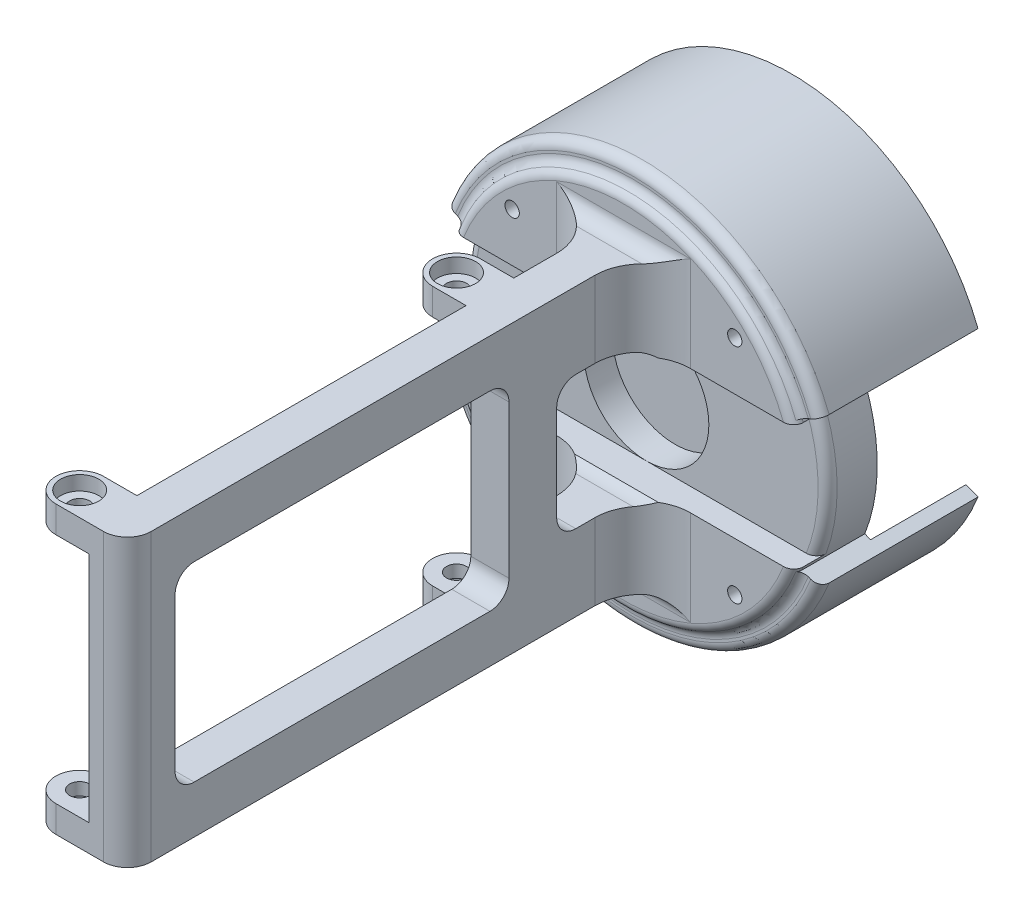
SolidWorks part; units mm, degrees
material "Esun Hard Tough Resin"
ref_plane "Front Plane" through (0, 0, 0) normal (0, 0, 1) x (1, 0, 0)
ref_plane "Top Plane" through (0, 0, 0) normal (0, 1, 0) x (1, 0, 0)
ref_plane "Right Plane" through (0, 0, 0) normal (1, 0, 0) x (0, 0, -1)
sketch "Sketch1" plane through (0, 0, 0) normal (0, 0, 1) x (1, 0, 0)
  line L0 (-11.6673, 11.6673) -> (11.6673, -11.6673) construction
  line L1 (11.6673, 11.6673) -> (-11.6673, -11.6673) construction
  line L2 (0, 16.5) -> (0, -16.5) construction
  circle A0 centre (0, 0) radius 19
  circle A1 centre (0, 0) radius 9 construction
  circle A2 centre (0, 0) radius 16.5 construction
  circle A3 centre (-11.6673, 11.6673) radius 1
  circle A4 centre (11.6673, 11.6673) radius 1
  circle A5 centre (11.6673, -11.6673) radius 1
  circle A6 centre (-11.6673, -11.6673) radius 1
  point P17 (0, 0)
  point P18 (0, 0)
  dimension "D1" = 38
  dimension "D2" = 18
  dimension "D3" = 33
  dimension "D4" = 2
  dimension "D5" = 90
  dimension "D6" = 45
extrude "Boss-Extrude1" add sketch "Sketch1" along normal blind 1.6
sketch "Sketch2" plane through (0, 0, 1.6) normal (0, 0, 1) x (1, 0, 0)
  circle A0 centre (0, 0) radius 19
  circle A1 centre (11.6673, -11.6673) radius 1 construction
  circle A2 centre (11.6673, 11.6673) radius 1 construction
  circle A3 centre (-11.6673, 11.6673) radius 1 construction
  circle A4 centre (-11.6673, -11.6673) radius 1 construction
  circle A5 centre (11.6673, -11.6673) radius 1 construction
  circle A6 centre (11.6673, 11.6673) radius 1 construction
  circle A7 centre (-11.6673, 11.6673) radius 1 construction
  circle A8 centre (-11.6673, -11.6673) radius 1 construction
  circle A9 centre (-11.6673, -11.6673) radius 0.75
  circle A10 centre (-11.6673, 11.6673) radius 0.75
  circle A11 centre (11.6673, 11.6673) radius 0.75
  circle A12 centre (11.6673, -11.6673) radius 0.75
  circle A13 centre (0, 0) radius 19 construction
  dimension "D1" = 1.5
extrude "Boss-Extrude2" add sketch "Sketch2" along normal blind 6
sketch "Sketch8" plane through (0, 0, 0) normal (0, 0, -1) x (-1, 0, 0)
  circle A0 centre (0, 0) radius 12.75
  dimension "D1" = 25.5
extrude "Cut-Extrude4" cut sketch "Sketch8" against normal blind 1
sketch "Sketch3" plane through (0, 0, 7.6) normal (0, 0, 1) x (1, 0, 0)
  circle A0 centre (0, 0) radius 6.55
  dimension "D1" = 13.1
extrude "Cut-Extrude1" cut sketch "Sketch3" against normal offset from surface (5.4 mm away) 1.2 up to face at (-12.75, 0, 1)
sketch "Sketch4" plane through (0, 0, 0) normal (1, 0, 0) x (0, 0, -1)
  line L0 (-7.6, 15) -> (-61.6, 15)
  line L1 (-7.6, 19) -> (-7.6, -19) construction
  line L2 (-61.6, 15) -> (-61.6, -15)
  line L3 (-61.6, -15) -> (-7.6, -15)
  line L4 (-7.6, -15) -> (-7.6, -7)
  line L5 (-7.6, -7) -> (-16.6, -7)
  line L6 (-16.6, -7) -> (-16.6, 7)
  line L7 (-16.6, 7) -> (-7.6, 7)
  line L8 (-7.6, 7) -> (-7.6, 15)
  point P6 (-16.6, 0)
  point P11 (-61.6, 0)
  dimension "D1" = 14
  dimension "D2" = 9
  dimension "D3" = 30
  dimension "D4" = 45
extrude "Boss-Extrude3" add sketch "Sketch4" along normal mid plane 4
fillet "Fillet1" radius 5 4 edges at (-2, -11, 7.6) (2, -11, 7.6) (2, 11, 7.6) (-2, 11, 7.6)
fillet "Fillet2" radius 2 2 edges at (0, -7, 16.6) (0, 7, 16.6)
ref_plane "Plane1" through (2, 15, 12.6) normal (0, 0, 1) x (1, 0, 0)
sketch "Sketch5" plane through (-2, 14.5, 12.6) normal (1, 0, 0) x (0, 0, -1)
  line L0 (0, 0.5) -> (-49, 0.5) construction
  line L1 (-49, 0.5) -> (-44, 0.5)
  line L2 (-49, 0.5) -> (-49, -2.3)
  line L3 (-49, -2.3) -> (-44, -2.3)
  line L4 (-44, 0.5) -> (-44, -2.3)
  line L5 (-9.5, 0.5) -> (-4.5, 0.5)
  line L6 (-9.5, 0.5) -> (-9.5, -2.3)
  line L7 (-9.5, -2.3) -> (-4.5, -2.3)
  line L8 (-4.5, 0.5) -> (-4.5, -2.3)
  line L9 (-1000, -14.5) -> (49000, -14.5) construction
  line L11 (-9.5, -26.7) -> (-4.5, -26.7)
  line L12 (-4.5, -29.5) -> (-4.5, -26.7)
  line L13 (-9.5, -29.5) -> (-4.5, -29.5)
  line L14 (-9.5, -29.5) -> (-9.5, -26.7)
  line L15 (-49, -26.7) -> (-44, -26.7)
  line L16 (-44, -29.5) -> (-44, -26.7)
  line L17 (-49, -29.5) -> (-44, -29.5)
  line L18 (-49, -29.5) -> (-49, -26.7)
  point P12 (-46.5, -2.3)
  point P17 (-7, -2.3)
  dimension "D1" = 39.5
  dimension "D2" = 5
  dimension "D3" = 2.8
extrude "Boss-Extrude4" add sketch "Sketch5" against normal blind 6
sketch "Sketch6" plane through (0, 15, 0) normal (0, 1, 0) x (1, 0, 0)
  line L0 (-8, -56.6) -> (-8, -61.6) construction
  line L1 (-8, -56.6) -> (-8, -61.6) construction
  line L2 (-8, -17.1) -> (-8, -22.1) construction
  line L3 (-8, -17.1) -> (-8, -22.1) construction
  circle A0 centre (-5.5, -59.1) radius 1.05
  circle A1 centre (-5.5, -19.6) radius 1.05
  point P7 (-8, -59.1)
  point P12 (-8, -19.6)
  dimension "D1" = 2.1
  dimension "D2" = 2.5
extrude "Cut-Extrude2" cut sketch "Sketch6" against normal through all
sketch "Sketch7" plane through (0, 15, 0) normal (0, 1, 0) x (1, 0, 0)
  circle A0 centre (-5.5, -19.6) radius 2
  circle A1 centre (-5.5, -59.1) radius 2
  dimension "D1" = 4
extrude "Cut-Extrude3" cut sketch "Sketch7" against normal blind 1.5
mirror "Mirror1" about plane through (0, 0, 0) normal (0, 1, 0) of "Cut-Extrude3"
fillet "Fillet3" radius 2.5 8 edges at (-8, -13.6, 61.6) (-8, -13.6, 56.6) (-8, 13.6, 61.6) (-8, 13.6, 56.6) (-8, -13.6, 22.1) (-8, -13.6, 17.1) (-8, 13.6, 22.1) (-8, 13.6, 17.1)
fillet "Fillet4" radius 2.5 1 edges at (2, 0, 61.6)
fillet "Fillet5" radius 1.5 2 edges at (0, -15, 7.6) (0, 15, 7.6)
fillet "Fillet6" radius 2 2 edges at (0, -7, 7.6) (0, 7, 7.6)
sketch "Sketch9" plane through (0, 0, 0) normal (0, 0, -1) x (-1, 0, 0)
  line L1 (-1, 14.9737) -> (1, 14.9737)
  line L2 (-1, 14.9737) -> (-1, 18.9737)
  line L4 (1, 14.9737) -> (1, 18.9737)
  circle A0 centre (0, 0) radius 19 construction
  circle A1 centre (0, 0) radius 19
  point P7 (0, 14.9737)
  circle M7 centre (0, 0) radius 19
  dimension "D1" = 2
  dimension "D2" = 4
extrude "Boss-Extrude5" add sketch "Sketch9" along normal blind 3 contours L1 L4 L2 M7
fillet "Fillet8" radius 1 1 edges at (19, 0, 7.6)
sketch "Sketch10" plane through (-2, 0, 0) normal (-1, 0, 0) x (0, 0, 1)
  line L0 (21.6, 10) -> (21.6, -10)
  line L1 (21.6, -10) -> (56.6, -10)
  line L2 (56.6, -10) -> (56.6, 10)
  line L3 (56.6, 10) -> (21.6, 10)
  line L4 (22.1, 15) -> (56.6, 15) construction
  line L5 (56.6, -15) -> (22.1, -15) construction
  line L6 (61.6, 12.2) -> (61.6, -12.2) construction
  line L7 (16.6, -5) -> (16.6, 5) construction
  dimension "D1" = 5
  dimension "D2" = 5
  dimension "D3" = 5
  dimension "D4" = 5
extrude "Cut-Extrude5" cut sketch "Sketch10" against normal through all
fillet "Fillet9" radius 2 4 edges at (0, 10, 56.6) (0, -10, 56.6) (0, -10, 21.6) (0, 10, 21.6)
fillet "Fillet10" radius 0.4 4 edges at (1, 16.9737, -3) (0, 19, -3) (-1, 16.9737, -3) (0, 14.9737, -3)
sketch "Sketch11" plane through (0, 0, 0) normal (1, 0, 0) x (0, 0, -1)
  line L0 (-2.2, 6.55) -> (-2.2, -6.55) construction
  line L1 (-2.2, 6.55) -> (-2.2, -6.55) construction
  line L3 (-5.2, 6.55) -> (-8.3361, 6.55)
  line L4 (-5.2, 6.55) -> (-5.2, -6.55)
  line L5 (-5.2, -6.55) -> (-8.3361, -6.55)
  line L6 (-8.3361, 6.55) -> (-8.3361, -6.55)
  arc A0 (-7.6, 5) -> (-9.6, 7) centre (-9.6, 5) ccw construction
  arc A1 (-7.6, 5) -> (-9.6, 7) centre (-9.6, 5) ccw construction
  dimension "D1" = 3
extrude "Cut-Extrude6" cut sketch "Sketch11" against normal through all both and the other way through all
fillet "Fillet11" radius 1 2 edges at (-19, 0, 5.2) (19, 0, 5.2)
sketch "Sketch12" plane through (0, 0, 0) normal (0, 0, -1) x (-1, 0, 0)
  line L0 (-19.5603, 7.6417) -> (19.5603, -7.6417)
  line L1 (-19.5603, -7.6417) -> (19.5603, 7.6417)
  arc A0 (16.766, -6.55) -> (16.766, 6.55) centre (0, 0) ccw construction
  arc A1 (-16.766, 6.55) -> (-16.766, -6.55) centre (0, 0) ccw construction
  arc A2 (-1, 18.9737) -> (1, 18.9737) centre (0, 0) ccw construction
  arc A3 (16.766, -6.55) -> (16.766, 6.55) centre (0, 0) ccw construction
  arc A4 (-16.766, 6.55) -> (-16.766, -6.55) centre (0, 0) ccw construction
  arc A5 (-1, 18.9737) -> (1, 18.9737) centre (0, 0) ccw construction
  circle A6 centre (0, 0) radius 21
  circle A7 centre (0, 0) radius 19
  point P12 (0, 0)
  point P15 (0, 0)
  arc M7 (-1, 18.9737) -> (1, 18.9737) centre (0, 0) ccw
  dimension "D1" = 42
extrude "Boss-Extrude6" add sketch "Sketch12" against normal up to vertex (6.6 mm away) contours A7 L1 A6 L0 M7 | L1 A6 L0 M7
sketch "Sketch13" plane through (0, 0, 0) normal (0, 0, -1) x (-1, 0, 0)
  line L0 (-19.5603, 7.6417) -> (-18.3028, 7.1504)
  line L1 (-19.5603, -7.6417) -> (-18.3028, -7.1504)
  line L2 (-19.5603, -7.6417) -> (-17.6974, -6.9139) construction
  line L3 (19.5603, 7.6417) -> (18.3028, 7.1504)
  line L4 (19.5603, -7.6417) -> (18.3028, -7.1504)
  line L5 (17.6974, -6.9139) -> (19.5603, -7.6417) construction
  arc A0 (-19.5603, -7.6417) -> (19.5603, -7.6417) centre (0, 0) ccw construction
  arc A1 (19.5603, 7.6417) -> (-19.5603, 7.6417) centre (0, 0) ccw construction
  arc A2 (-19.5603, -7.6417) -> (19.5603, -7.6417) centre (0, 0) ccw
  arc A3 (19.5603, 7.6417) -> (-19.5603, 7.6417) centre (0, 0) ccw
  circle A4 centre (0, 0) radius 19.65
  line M3 (17.6974, 6.9139) -> (19.5603, 7.6417)
  arc M4 (19.5603, 7.6417) -> (-19.5603, 7.6417) centre (0, 0) ccw
  line M5 (-19.5603, 7.6417) -> (-17.6974, 6.9139)
  line M7 (17.6974, 6.9139) -> (19.5603, 7.6417)
  arc M8 (19.5603, 7.6417) -> (-19.5603, 7.6417) centre (0, 0) ccw
  line M9 (-19.5603, 7.6417) -> (-17.6974, 6.9139)
  dimension "D1" = 39.3
extrude "Boss-Extrude7" add sketch "Sketch13" along normal blind 10 contours A4 M3 M4 M5 | A4 M7 M8 M9
fillet "Fillet12" radius 1 4 edges at (0, -19, 6.6) (0, 19, 6.6) (0, -21, 6.6) (0, 21, 6.6)
equation "\"D2@Sketch10\"=\"D1@Sketch10\""
equation "\"D3@Sketch10\"=\"D1@Sketch10\""
equation "\"D4@Sketch10\"=\"D1@Sketch10\""
